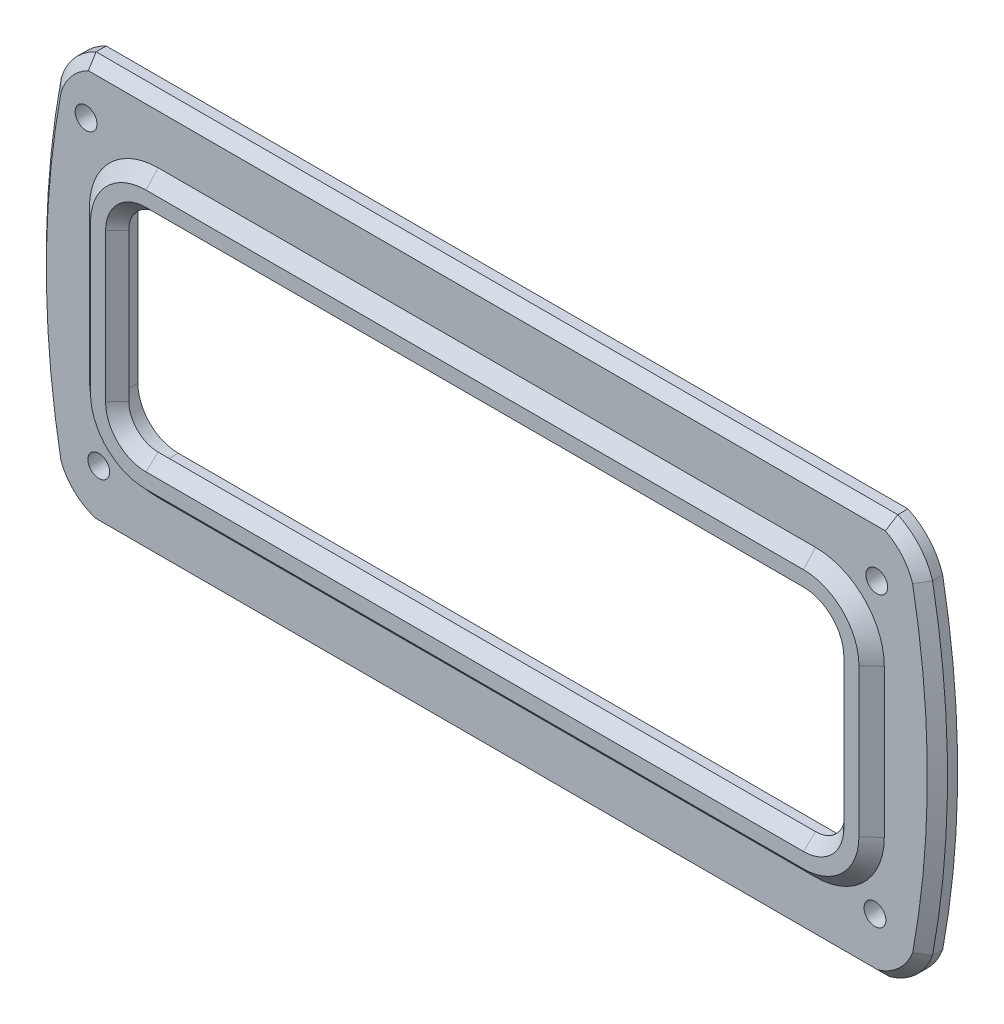
SolidWorks part; units mm, degrees
material "PLA"
ref_plane "Front Plane" through (0, 0, 0) normal (0, 0, 1) x (1, 0, 0)
ref_plane "Top Plane" through (0, 0, 0) normal (0, 1, 0) x (1, 0, 0)
ref_plane "Right Plane" through (0, 0, 0) normal (1, 0, 0) x (0, 0, -1)
sketch "Sketch1" plane through (0, 0, 0) normal (0, 0, 1) x (1, 0, 0)
  line L6 (0, 25) -> (0, -25) construction
  line L7 (49.5862, 25) -> (-49.5862, 25)
  line L8 (-48.5482, -25) -> (48.5482, -25)
  line L11 (-55.74, 0) -> (55.74, 0) construction
  line L13 (-40.665, 14.165) -> (40.665, 14.165)
  line L14 (-45.665, 9.165) -> (-45.665, -9.165)
  line L15 (-40.665, -14.165) -> (40.665, -14.165)
  line L16 (45.665, 9.165) -> (45.665, -9.165)
  arc A0 (-49.5862, 25) -> (-53.8902, 20.0694) centre (-46.2582, 17.7511) ccw
  arc A1 (-53.8902, 20.0694) -> (-53.8902, -20.0694) centre (54.0547, 0) ccw
  arc A2 (-53.8902, -20.0694) -> (-48.5482, -25) centre (-46.4036, -17.3174) ccw
  arc A3 (48.5482, -25) -> (53.8902, -20.0694) centre (46.4036, -17.3174) ccw
  arc A4 (53.8902, -20.0694) -> (53.8902, 20.0694) centre (-54.0547, 0) ccw
  arc A5 (53.8902, 20.0694) -> (49.5862, 25) centre (46.2582, 17.7511) ccw
  arc A6 (40.665, 14.165) -> (45.665, 9.165) centre (40.665, 9.165) cw
  arc A7 (40.665, -14.165) -> (45.665, -9.165) centre (40.665, -9.165) ccw
  arc A8 (-45.665, -9.165) -> (-40.665, -14.165) centre (-40.665, -9.165) ccw
  arc A9 (-40.665, 14.165) -> (-45.665, 9.165) centre (-40.665, 9.165) ccw
  point P2 (0, 0)
  point P24 (0, 14.165)
  point P25 (-45.665, 0)
  point P28 (45.665, 14.165)
  point P33 (-45.665, -14.165)
  point P36 (-45.665, 14.165)
  dimension "D3" = 5
  dimension "D1" = 28.33
  dimension "D2" = 91.33
  dimension "D4" = 111.48
  dimension "D5" = 55.74
  dimension "D6" = 50
  dimension "D7" = 25
extrude "Boss-Extrude1" add sketch "Sketch1" along normal blind 2.5
chamfer "Chamfer1" distance 1.25 angle 45 8 edges at (51.8136, -23.1787, 2.5) (0, -25, 2.5) (55.74, 0, 2.5) (-51.8136, -23.1787, 2.5) (52.2672, 22.9965, 2.5) (-55.74, 0, 2.5) (-52.2672, 22.9965, 2.5) (0, 25, 2.5)
sketch "Sketch2" plane through (0, 0, 2.5) normal (0, 0, 1) x (1, 0, 0)
  line L0 (-52.2672, 22.9965) -> (-44.2005, 12.7005) construction
  line L1 (-44.2005, -12.7005) -> (-51.8136, -23.1787) construction
  line L2 (44.2005, -12.7005) -> (51.8136, -23.1787) construction
  line L3 (52.2672, 22.9965) -> (44.2005, 12.7005) construction
  circle A4 centre (-48.007, -17.9396) radius 1.35
  circle A5 centre (-49.575, 18.5555) radius 1.35
  circle A6 centre (48.2339, 17.8485) radius 1.35
  circle A7 centre (48.007, -17.9396) radius 1.35
  arc A12 (40.665, -14.165) -> (45.665, -9.165) centre (40.665, -9.165) ccw construction
  arc A13 (48.5482, -25) -> (53.8902, -20.0694) centre (46.4036, -17.3174) ccw construction
  arc A14 (53.8902, 20.0694) -> (49.5862, 25) centre (46.2582, 17.7511) ccw construction
  arc A15 (45.665, 9.165) -> (40.665, 14.165) centre (40.665, 9.165) ccw construction
  arc A16 (-45.665, -9.165) -> (-40.665, -14.165) centre (-40.665, -9.165) ccw construction
  arc A17 (-53.8902, -20.0694) -> (-48.5482, -25) centre (-46.4036, -17.3174) ccw construction
  arc A18 (-49.5862, 25) -> (-53.8902, 20.0694) centre (-46.2582, 17.7511) ccw construction
  arc A19 (-40.665, 14.165) -> (-45.665, 9.165) centre (-40.665, 9.165) ccw construction
  point P35 (-48.007, -17.9396)
  point P41 (48.007, -17.9396)
  point P42 (48.2339, 17.8485)
  dimension "D1" = 2.7
extrude "Cut-Extrude1" cut sketch "Sketch2" against normal through all
sketch "Sketch3" plane through (0, 0, 2.5) normal (0, 0, 1) x (1, 0, 0)
  line L31 (49.165, -9.165) -> (49.165, 9.165)
  line L32 (-40.665, -17.665) -> (40.665, -17.665)
  line L33 (-49.165, 9.165) -> (-49.165, -9.165)
  line L34 (40.665, 17.665) -> (-40.665, 17.665)
  line L35 (49.165, -9.165) -> (49.165, 9.165)
  line L36 (-40.665, -17.665) -> (40.665, -17.665)
  line L37 (-49.165, 9.165) -> (-49.165, -9.165)
  line L38 (40.665, 17.665) -> (-40.665, 17.665)
  line L59 (44.165, -9.165) -> (44.165, 9.165)
  line L60 (-40.665, -12.665) -> (40.665, -12.665)
  line L61 (-44.165, 9.165) -> (-44.165, -9.165)
  line L62 (40.665, 12.665) -> (-40.665, 12.665)
  line L63 (44.165, -9.165) -> (44.165, 9.165)
  line L64 (-40.665, -12.665) -> (40.665, -12.665)
  line L65 (-44.165, 9.165) -> (-44.165, -9.165)
  line L66 (40.665, 12.665) -> (-40.665, 12.665)
  arc A21 (49.165, 9.165) -> (40.665, 17.665) centre (40.665, 9.165) ccw
  arc A22 (40.665, -17.665) -> (49.165, -9.165) centre (40.665, -9.165) ccw
  arc A23 (-49.165, -9.165) -> (-40.665, -17.665) centre (-40.665, -9.165) ccw
  arc A24 (-40.665, 17.665) -> (-49.165, 9.165) centre (-40.665, 9.165) ccw
  arc A25 (49.165, 9.165) -> (40.665, 17.665) centre (40.665, 9.165) ccw
  arc A26 (40.665, -17.665) -> (49.165, -9.165) centre (40.665, -9.165) ccw
  arc A27 (-49.165, -9.165) -> (-40.665, -17.665) centre (-40.665, -9.165) ccw
  arc A28 (-40.665, 17.665) -> (-49.165, 9.165) centre (-40.665, 9.165) ccw
  arc A45 (44.165, 9.165) -> (40.665, 12.665) centre (40.665, 9.165) ccw
  arc A46 (40.665, -12.665) -> (44.165, -9.165) centre (40.665, -9.165) ccw
  arc A47 (-44.165, -9.165) -> (-40.665, -12.665) centre (-40.665, -9.165) ccw
  arc A48 (-40.665, 12.665) -> (-44.165, 9.165) centre (-40.665, 9.165) ccw
  arc A49 (44.165, 9.165) -> (40.665, 12.665) centre (40.665, 9.165) ccw
  arc A50 (40.665, -12.665) -> (44.165, -9.165) centre (40.665, -9.165) ccw
  arc A51 (-44.165, -9.165) -> (-40.665, -12.665) centre (-40.665, -9.165) ccw
  arc A52 (-40.665, 12.665) -> (-44.165, 9.165) centre (-40.665, 9.165) ccw
  dimension "D1" = 3.5
  dimension "D2" = 1.5
extrude "Boss-Extrude2" add sketch "Sketch3" along normal blind 1.5
chamfer "Chamfer2" distance 1.5 angle 47.5 16 edges at (-43.1399, 11.6399, 4) (-44.165, 0, 4) (-43.1399, -11.6399, 4) (0, -12.665, 4) (43.1399, -11.6399, 4) (44.165, 0, 4) (43.1399, 11.6399, 4) (0, 12.665, 4) (49.165, 0, 4) (46.6754, -15.1754, 4) (0, -17.665, 4) (-46.6754, -15.1754, 4) (-49.165, 0, 4) (-46.6754, 15.1754, 4) (0, 17.665, 4) (46.6754, 15.1754, 4) first distance on face at (0, 0, 4) first distance on face at (49.165, 0, 3.25) first distance on face at (45.7952, -14.2952, 3.25) first distance on face at (0, -17.665, 3.25) first distance on face at (-45.7952, -14.2952, 3.25) first distance on face at (-49.165, 0, 3.25) first distance on face at (-45.7952, 14.2952, 3.25) first distance on face at (0, 17.665, 3.25) first distance on face at (45.7952, 14.2952, 3.25)
sketch "Sketch6" plane through (0, 0, 2.5) normal (0, 0, 1) x (1, 0, 0)
  line L0 (-54.49, 0.0187) -> (54.49, 0.0187) construction
  line L1 (0, 0.0187) -> (0, -31.0541) construction
  arc A0 (-52.6744, 19.7699) -> (-52.6812, -19.733) centre (54.0547, 0) ccw construction
  arc A1 (52.6812, -19.733) -> (52.6744, 19.7699) centre (-54.0547, 0) ccw construction
